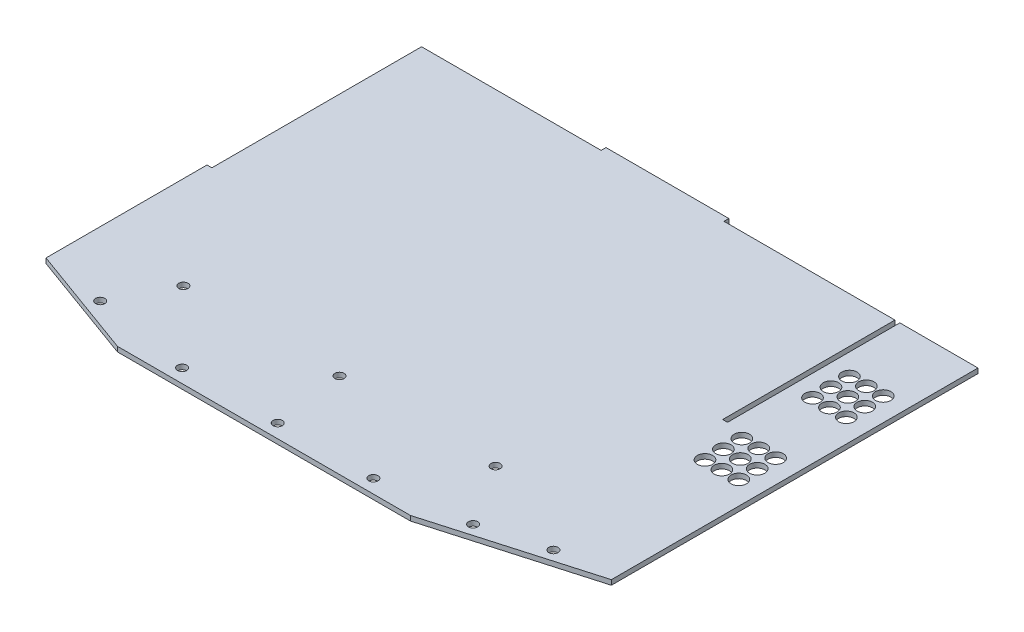
SolidWorks part; units mm, degrees
material "6061-T6 (SS)"
ref_plane "X-Y Datum" through (0, 0, 0) normal (0, 0, 1) x (1, 0, 0)
ref_plane "X-Z Datum" through (0, 0, 0) normal (0, 1, 0) x (1, 0, 0)
ref_plane "Y-Z Datum" through (0, 0, 0) normal (1, 0, 0) x (0, 0, -1)
sketch "Sketch1" plane through (0, 0, 0) normal (0, 0, 1) x (1, 0, 0)
  line L1 (-154.0556, -1.5875) -> (154.0556, -1.5875)
  line L2 (-154.0556, -1.5875) -> (-154.0556, 1.5875)
  line L3 (-154.0556, 1.5875) -> (154.0556, 1.5875)
  line L4 (154.0556, -1.5875) -> (154.0556, 1.5875)
  line L5 (-154.0556, -1.5875) -> (154.0556, 1.5875) construction
  line L6 (-154.0556, 1.5875) -> (154.0556, -1.5875) construction
  point P0 (0, 0)
  dimension "D1" = 3.175
  dimension "D2" = 308.1112
extrude "Boss-Extrude1" add sketch "Sketch1" along normal blind 267.83
sketch "Sketch3" plane through (154.0556, 0, 0) normal (1, 0, 0) x (0, 0, -1)
  line L0 (-267.83, 1.5875) -> (0, 1.5875) construction
  line L1 (-267.83, -1.5875) -> (-112.128, -1.5875)
  line L2 (-267.83, -1.5875) -> (-267.83, 1.5875)
  line L3 (-267.83, 1.5875) -> (-112.128, 1.5875)
  line L4 (-112.128, -1.5875) -> (-112.128, 1.5875)
  dimension "D1" = 155.702
extrude "Boss-Extrude3" add sketch "Sketch3" along normal blind 3.175
sketch "Sketch4" plane through (0, 0, 267.83) normal (0, 0, 1) x (1, 0, 0)
  line L1 (157.2306, -1.5875) -> (208.1043, -1.5875)
  line L2 (157.2306, -1.5875) -> (157.2306, 1.5875)
  line L3 (157.2306, 1.5875) -> (208.1043, 1.5875)
  line L4 (208.1043, -1.5875) -> (208.1043, 1.5875)
  dimension "D1" = 3.175
  dimension "D2" = 50.8737
extrude "Boss-Extrude4" add sketch "Sketch4" against normal blind 267.83
sketch "Sketch6" plane through (0, 1.5875, 0) normal (0, 1, 0) x (1, 0, 0)
  line L0 (106.5043, -267.83) -> (106.5043, -223.38)
  line L1 (208.1043, -267.83) -> (-154.0556, -267.83) construction
  line L2 (208.1043, -223.38) -> (106.5043, -223.38)
  line L3 (208.1043, 0) -> (208.1043, -267.83) construction
  line L5 (106.5043, -267.83) -> (208.1047, -238.62)
  line L6 (208.1043, -223.38) -> (208.1047, -238.62)
  line M9 (-154.0556, -267.83) -> (208.1043, -267.83)
  line M10 (208.1043, -267.83) -> (208.1043, 0)
  dimension "D1" = 44.45
  dimension "D2" = 101.6
  dimension "D3" = 15.24
extrude "Cut-Extrude1" cut sketch "Sketch6" against normal through all contours L5 M9 M10 region at (174.2376, 1.5875, 258.0934)
sketch "Sketch11" plane through (0, -1.5875, 0) normal (0, -1, 0) x (1, 0, 0)
  line L0 (-84.2056, 267.83) -> (-84.2056, 242.43)
  line L1 (-154.0556, 267.83) -> (106.5043, 267.83) construction
  line L2 (-154.0556, 242.43) -> (-84.2056, 242.43)
  line L3 (-154.0556, 267.83) -> (-154.0556, 0) construction
  line L4 (-154.0556, 242.43) -> (-84.2056, 267.83)
  line M4 (-154.0556, 267.83) -> (-154.0556, 0)
  line M18 (106.5043, 267.83) -> (-154.0556, 267.83)
  dimension "D1" = 69.85
  dimension "D2" = 25.4
extrude "Cut-Extrude3" cut sketch "Sketch11" against normal through all contours L4 M4 M18 region at (-130.7723, -1.5875, 259.3633)
sketch "Sketch13" plane through (0, -1.5875, 0) normal (0, -1, 0) x (1, 0, 0)
  circle A6 centre (171.0499, 116.6448) radius 5
  circle A7 centre (182.0499, 116.6448) radius 5
  circle A8 centre (193.0499, 116.6448) radius 5
  circle A9 centre (171.0499, 46.6448) radius 5
  circle A10 centre (182.0499, 46.6448) radius 5
  circle A11 centre (193.0499, 46.6448) radius 5
extrude "Cut-Extrude4" cut sketch "Sketch13" against normal through all
pattern_linear "LPattern1" count 3 spacing 12 along (0, 0, 1) of "Cut-Extrude4"
sketch "Sketch17" plane through (-154.0556, 0, 0) normal (-1, 0, 0) x (0, 0, 1)
  line L0 (136.4994, 1.5875) -> (136.4994, -1.5875)
  line L5 (242.43, 1.5875) -> (136.4994, 1.5875)
  line L9 (242.43, -1.5875) -> (0, -1.5875) construction
  line L10 (136.4994, -1.5875) -> (242.43, -1.5875)
  line L11 (242.43, -1.5875) -> (242.43, 1.5875)
extrude "Boss-Extrude5" add sketch "Sketch17" along normal blind 3.175
sketch "Sketch18" plane through (0, 0, 0) normal (0, 0, -1) x (-1, 0, 0)
  line L0 (-154.0556, 1.5875) -> (154.0556, 1.5875) construction
  line L1 (-42.784, 1.5875) -> (37.216, 1.5875)
  line L2 (-42.784, 1.5875) -> (-42.784, -1.5875)
  line L3 (-42.784, -1.5875) -> (37.216, -1.5875)
  line L4 (37.216, 1.5875) -> (37.216, -1.5875)
  line L5 (-42.784, 1.5875) -> (-42.784, -1.5875) construction
  line L6 (154.0556, -1.5875) -> (-154.0556, -1.5875) construction
  line L7 (37.216, 1.5875) -> (37.216, -1.5875) construction
extrude "Boss-Extrude6" add sketch "Sketch18" along normal blind 3.175
sketch "Sketch22" plane through (0, 1.5875, 0) normal (0, 1, 0) x (1, 0, 0)
  circle A0 centre (-96.7719, -212.3068) radius 0.0276
  circle A1 centre (-96.7719, -212.3068) radius 3
  dimension "D1" = 6
extrude "Cut-Extrude6" cut sketch "Sketch22" against normal through all
pattern_linear "LPattern2" count 3 spacing 101.6 along (1, 0, 0) of "Cut-Extrude6"
sketch "Sketch23" plane through (0, 1.5875, 0) normal (0, 1, 0) x (1, 0, 0)
  line L0 (-154.0556, -242.43) -> (-157.2306, -241.2755)
  line L1 (-157.2306, -242.43) -> (-157.2306, -136.4994) construction
  line L2 (-154.0556, -242.43) -> (-84.2056, -267.83) construction
  line L3 (-154.0556, -242.43) -> (-84.2056, -267.83) construction
extrude "Cut-Extrude7" cut sketch "Sketch23" against normal through all and the other way through all
sketch "Sketch25" plane through (0, -1.5875, 0) normal (0, -1, 0) x (1, 0, 0)
  line L0 (-157.2306, 241.2755) -> (-83.9957, 267.9063) construction
  line L1 (-50.9757, 267.83) -> (-50.9757, 258.94)
  line L2 (-157.2306, 241.2755) -> (-84.2056, 267.83) construction
  line L3 (-118.0827, 255.5111) -> (-115.3206, 247.9154)
  line L4 (-157.2306, 136.4994) -> (-157.2306, 241.2755) construction
  line L5 (-84.2056, 267.83) -> (106.5043, 267.83) construction
  line L6 (-50.9757, 258.94) -> (11.2543, 258.94) construction
  line L7 (11.2543, 258.94) -> (73.4843, 258.94) construction
  line L8 (172.5443, 248.8436) -> (172.5443, 240.7613)
  line L9 (106.5043, 267.83) -> (208.1043, 238.6201) construction
  line L10 (172.5443, 240.7613) -> (131.9043, 252.4453) construction
  circle A0 centre (-115.3206, 247.9154) radius 3
  circle A1 centre (-50.9757, 258.94) radius 3
  circle A2 centre (11.2543, 258.94) radius 3
  circle A3 centre (73.4843, 258.94) radius 3
  circle A4 centre (172.5443, 240.7613) radius 3
  circle A5 centre (131.9043, 252.4453) radius 3
  dimension "D2" = 90
  dimension "D3" = 6
  dimension "D13" = 8.89
  dimension "D1" = 8.0823
  dimension "D4" = 41.91
  dimension "D5" = 33.02
  dimension "D6" = 62.23
  dimension "D7" = 62.23
  dimension "D8" = 33.02
  dimension "D9" = 35.56
  dimension "D10" = 73.96
  dimension "D11" = 40.64
  dimension "D12" = 8.0823
extrude "Cut-Extrude8" cut sketch "Sketch25" against normal blind 3.175 contours A0 | A1 | A2 | A5 | A4 | A3 region at (-116.993, -1.5875, 245.5277) region at (-53.0371, -1.5875, 256.8787) region at (11.2543, -1.5875, 258.94) region at (170.4829, -1.5875, 238.7) region at (131.9043, -1.5875, 252.4453)
